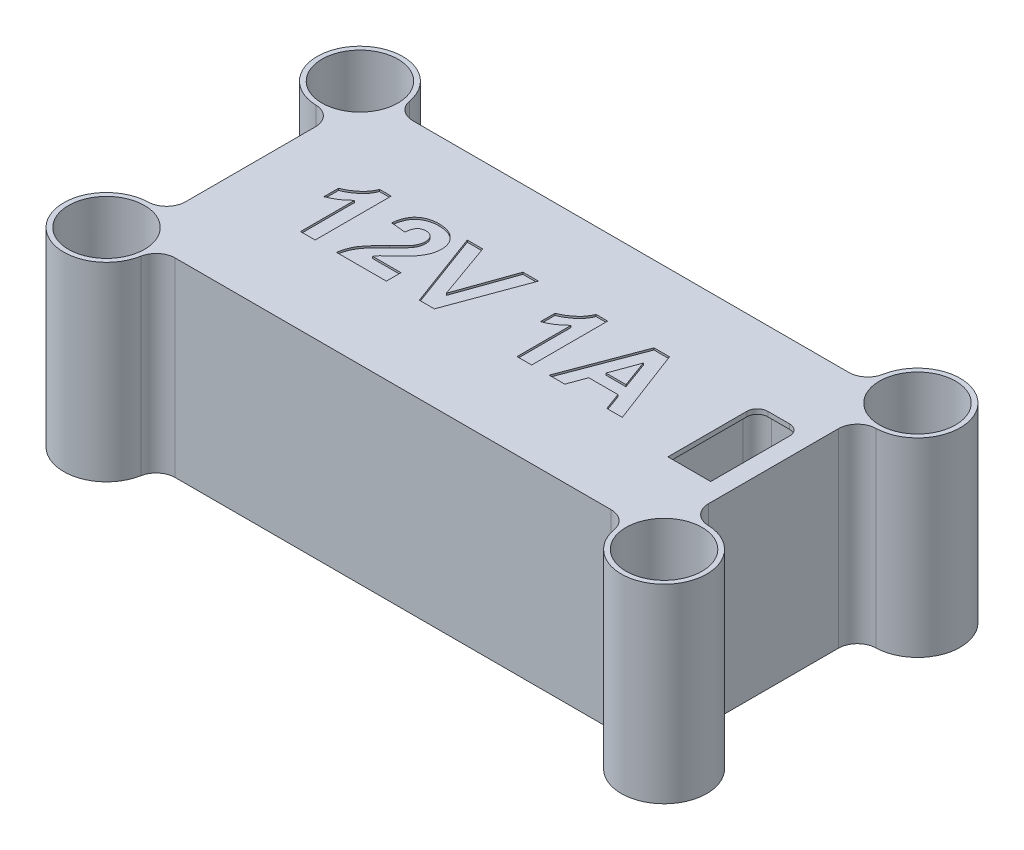
SolidWorks part; units mm, degrees
ref_plane "Front Plane" through (0, 0, 0) normal (0, 0, 1) x (1, 0, 0)
ref_plane "Top Plane" through (0, 0, 0) normal (0, 1, 0) x (1, 0, 0)
ref_plane "Right Plane" through (0, 0, 0) normal (1, 0, 0) x (0, 0, -1)
sketch "Sketch1" plane through (0, 0, 0) normal (0, 1, 0) x (1, 0, 0)
  line L0 (0, 12.5) -> (0, -12.5) construction
  line L1 (-27.5, 12.5) -> (27.5, 12.5)
  line L2 (-27.5, 12.5) -> (-27.5, -12.5)
  line L3 (-27.5, -12.5) -> (27.5, -12.5)
  line L4 (27.5, 12.5) -> (27.5, -12.5)
  line L5 (-27.5, 12.5) -> (27.5, -12.5) construction
  line L6 (-27.5, -12.5) -> (27.5, 12.5) construction
  line L7 (-27.5, 0) -> (27.5, 0) construction
  line L8 (-24.8207, 13.3276) -> (-24.8207, 12.5)
  line L9 (-29.3207, 8.8276) -> (-27.5, 8.8276)
  line L10 (24.8207, 13.3276) -> (24.8207, 12.5)
  line L11 (29.3207, 8.8276) -> (27.5, 8.8276)
  line L12 (29.3207, -8.8276) -> (27.5, -8.8276)
  line L13 (24.8207, -13.3276) -> (24.8207, -12.5)
  line L14 (-24.8207, -13.3276) -> (-24.8207, -12.5)
  line L15 (-29.3207, -8.8276) -> (-27.5, -8.8276)
  circle A0 centre (-29.3207, 13.3276) radius 2
  circle A1 centre (-29.3207, 13.3276) radius 4.5
  circle A2 centre (29.3207, 13.3276) radius 2
  circle A3 centre (29.3207, 13.3276) radius 4.5
  circle A4 centre (29.3207, -13.3276) radius 2
  circle A5 centre (29.3207, -13.3276) radius 4.5
  circle A6 centre (-29.3207, -13.3276) radius 2
  circle A7 centre (-29.3207, -13.3276) radius 4.5
  point P0 (0, 0)
  dimension "D3" = 4
  dimension "D4" = 9
  dimension "D1" = 25
  dimension "D2" = 55
extrude "Boss-Extrude1" add sketch "Sketch1" along normal blind 20 contours A7 L3 A6 L2 | L3 A7 L14 | A7 L2 L3 | L15 A7 L2 | L2 A7 L3 A5 L4 A3 L1 A1 | A1 L9 L2 | A1 L2 A0 L1 | L2 A1 L1 | A1 L1 L8 | L11 A3 L4 | L1 A3 L10 | A3 L4 L1 | A3 L1 A2 L4 | A5 L12 L4 | A5 L3 L13 | L4 A5 L3 | A5 L4 A4 L3 region at (0, 0, 0) region at (-24.8437, 0, -12.7065) region at (24.8437, 0, -12.7065) region at (-26.4801, 0, -11.2313) region at (-26.1987, 0, -12.6273) region at (24.9667, 0, -12.9238) region at (26.4801, 0, -11.2313) region at (-27.9512, 0, -8.9421) region at (27.9512, 0, -8.9421) region at (-27.9512, 0, 8.9421) region at (27.9512, 0, 8.9421) region at (-26.4801, 0, 11.2313) region at (-27.6273, 0, 10.8562) region at (28.4166, 0, 9.0494) region at (26.4801, 0, 11.2313) region at (-24.8437, 0, 12.7065) region at (24.8437, 0, 12.7065)
sketch "Sketch2" plane through (0, 20, 0) normal (0, 1, 0) x (1, 0, 0)
  line L0 (0, 12.5) -> (0, -12.5) construction
  line L1 (-24.8207, 12.5) -> (24.8207, 12.5) construction
  line L2 (-24.8207, -12.5) -> (24.8207, -12.5) construction
  line L3 (-27.5, 0) -> (27.5, 0) construction
  line L4 (-27.5, 8.8276) -> (-27.5, -8.8276) construction
  line L5 (27.5, 8.8276) -> (27.5, -8.8276) construction
  circle A0 centre (-29.3207, 13.3276) radius 4
  arc A1 (-24.8207, 13.3276) -> (-29.3207, 8.8276) centre (-29.3207, 13.3276) ccw construction
  circle A2 centre (29.3207, 13.3276) radius 4
  circle A3 centre (29.3207, -13.3276) radius 4
  circle A4 centre (-29.3207, -13.3276) radius 4
  dimension "D1" = 0.5
extrude "Cut-Extrude1" cut sketch "Sketch2" against normal offset from surface (18.5 mm away) 1.5 up to face at (0, 0, 0)
sketch "Sketch3" plane through (0, 20, 0) normal (0, 1, 0) x (1, 0, 0)
  line L0 (-27.5, 0) -> (27.5, 0) construction
  line L1 (-27.5, 8.8276) -> (-27.5, -8.8276) construction
  line L2 (27.5, 8.8276) -> (27.5, -8.8276) construction
  line L3 (23.35, 12.5) -> (23.35, -12.5) construction
  line L4 (-24.8207, 12.5) -> (24.8207, 12.5) construction
  line L5 (-24.8207, -12.5) -> (24.8207, -12.5) construction
  line L7 (22.2, 5.1) -> (24.5, 5.1)
  line L8 (20.7, 3.6) -> (20.7, -5.1)
  line L9 (20.7, -5.1) -> (26, -5.1)
  line L10 (26, 3.6) -> (26, -5.1)
  line L11 (20.7, 5.1) -> (26, -5.1) construction
  line L12 (20.7, -5.1) -> (26, 5.1) construction
  arc A0 (24.5, 5.1) -> (26, 3.6) centre (24.5, 3.6) cw
  arc A1 (22.2, 5.1) -> (20.7, 3.6) centre (22.2, 3.6) ccw
  point P12 (23.35, 0)
  dimension "D4" = 1.5
  dimension "D1" = 1.5
  dimension "D2" = 10.2
  dimension "D3" = 5.3
extrude "Cut-Extrude2" cut sketch "Sketch3" against normal up to next from offset 0.5 offset against normal yes
sketch "Sketch5" plane through (0, 0, 0) normal (0, -1, 0) x (1, 0, 0)
  line L0 (-27.5, 0) -> (-26, 0) construction
  line L1 (26, -11) -> (-26, -11)
  line L2 (26, -11) -> (26, 11)
  line L3 (26, 11) -> (-26, 11)
  line L4 (-26, -11) -> (-26, 11)
  line L5 (26, -11) -> (-26, 11) construction
  line L6 (26, 11) -> (-26, -11) construction
  line L7 (-27.5, -8.8276) -> (-27.5, 8.8276) construction
  line L8 (0, 11) -> (0, 12.5) construction
  line L9 (-24.8207, 12.5) -> (24.8207, 12.5) construction
  line L10 (19.2, 11) -> (19.2, -11)
  line L11 (19.2, 0) -> (20.7, 0) construction
  line L13 (19.2, 6.6) -> (26, 6.6)
  line L14 (23.35, 5.1) -> (23.35, 6.6) construction
  line L16 (19.2, -6.6) -> (26, -6.6)
  line L17 (26, 5.1) -> (20.7, 5.1) construction
  line L18 (20.7, 5.1) -> (20.7, -3.6) construction
  point P0 (0, 0)
  point P28 (0, 0)
  point P29 (0, 0)
  dimension "D1" = 1.5
extrude "Cut-Extrude4" cut sketch "Sketch5" against normal offset from surface (18.5 mm away) 1.5 contours L10 L3 L4 L1 | L10 L13 L2 L3 | L16 L10 L1 L2 region at (22.6, 0, -8.8) region at (-3.4, 0, 0) region at (22.6, 0, 8.8) up to face at (29.3207, 20, -17.3276)
sketch "Sketch7" plane through (0, 19.5, 0) normal (0, -1, 0) x (1, 0, 0)
  line L8 (25.6, -3.6) -> (25.6, 4.7)
  line L9 (25.6, 4.7) -> (21.1, 4.7)
  line L10 (21.1, 4.7) -> (21.1, -3.6)
  line L11 (22.2, -4.7) -> (24.5, -4.7)
  line L12 (25.6, -3.6) -> (25.6, 4.7)
  line L13 (25.6, 4.7) -> (21.1, 4.7)
  line L14 (21.1, 4.7) -> (21.1, -3.6)
  line L15 (22.2, -4.7) -> (24.5, -4.7)
  arc A4 (21.1, -3.6) -> (22.2, -4.7) centre (22.2, -3.6) ccw
  arc A5 (24.5, -4.7) -> (25.6, -3.6) centre (24.5, -3.6) ccw
  arc A6 (21.1, -3.6) -> (22.2, -4.7) centre (22.2, -3.6) ccw
  arc A7 (24.5, -4.7) -> (25.6, -3.6) centre (24.5, -3.6) ccw
  dimension "D1" = 0.4
extrude "Cut-Extrude6" cut sketch "Sketch7" against normal up to next
sketch "Sketch8" plane through (0, 0, 0) normal (0, -1, 0) x (1, 0, 0)
  line L1 (19.2, 6.6) -> (26, 6.6)
  line L2 (19.2, 6.6) -> (19.2, -6.6)
  line L3 (19.2, -6.6) -> (26, -6.6)
  line L4 (26, 6.6) -> (26, -6.6)
extrude "Cut-Extrude7" cut sketch "Sketch8" against normal offset from surface (8.8 mm away) 10.7 up to face at (23.35, 19.5, -1.2759)
fillet "Fillet1" radius 2 8 edges at (-24.8207, 10, 12.5) (27.5, 10, -8.8276) (27.5, 10, 8.8276) (-24.8207, 10, -12.5) (24.8207, 10, -12.5) (-27.5, 10, 8.8276) (24.8207, 10, 12.5) (-27.5, 10, -8.8276)
sketch "Sketch9" plane through (0, 20, 0) normal (0, 1, 0) x (1, 0, 0)
  line L0 (-27.5, -3.5033) -> (21.1, -3.5033) construction
  line L1 (-27.5, 6.8301) -> (-27.5, -6.8301) construction
  line L3 (21.1, -4.7) -> (21.1, 3.6) construction
  text T0 "12V 1A" font "Arial" height 8
extrude "Cut-Extrude8" cut sketch "Sketch9" against normal blind 0.2
